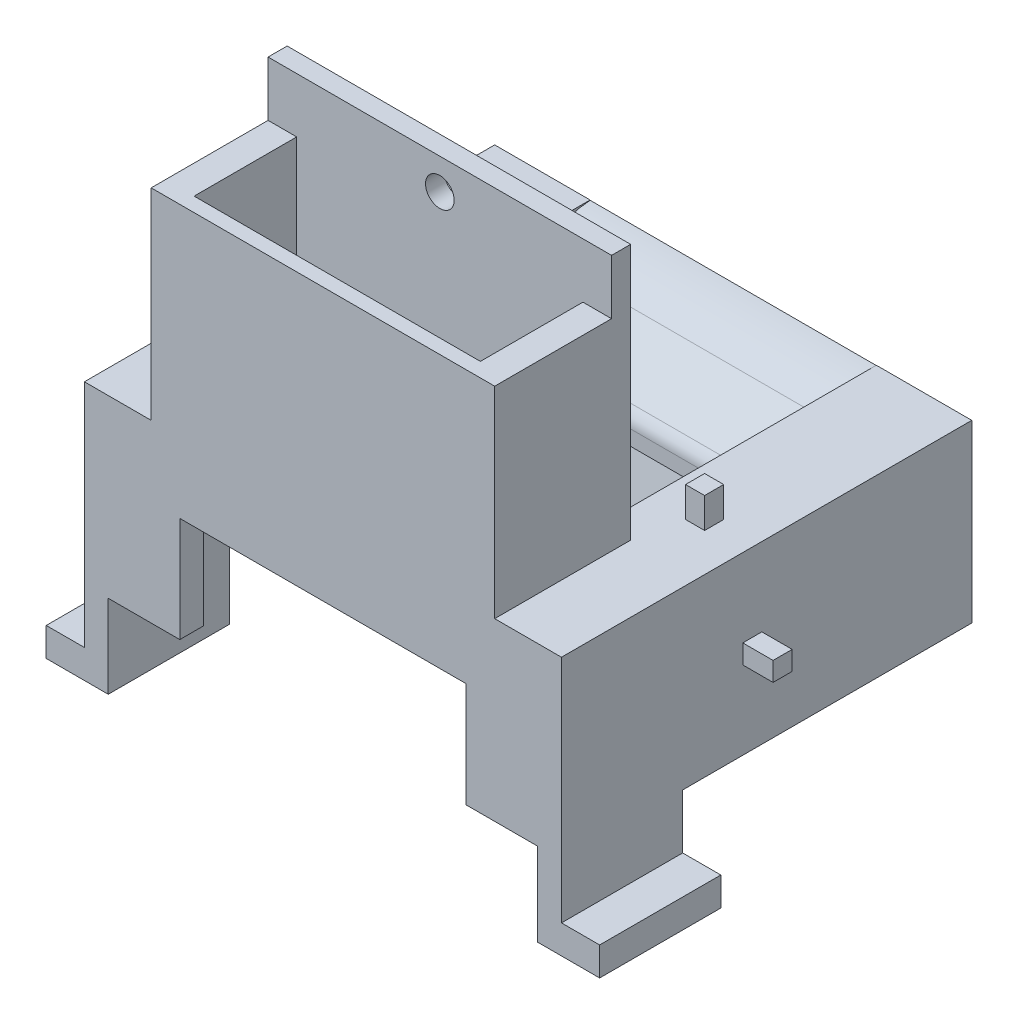
SolidWorks part; units mm, degrees
ref_plane "Front Plane" through (0, 0, 0) normal (0, 0, 1) x (1, 0, 0)
ref_plane "Top Plane" through (0, 0, 0) normal (0, 1, 0) x (1, 0, 0)
ref_plane "Right Plane" through (0, 0, 0) normal (1, 0, 0) x (0, 0, -1)
sketch "Sketch1" plane through (0, 0, 0) normal (0, 0, 1) x (1, 0, 0)
  line L1 (-25, 9.2) -> (25, 9.2)
  line L2 (-25, 9.2) -> (-25, -9.2)
  line L3 (-25, -9.2) -> (25, -9.2)
  line L4 (25, 9.2) -> (25, -9.2)
  line L5 (-25, 9.2) -> (25, -9.2) construction
  line L6 (-25, -9.2) -> (25, 9.2) construction
  point P0 (0, 0)
  dimension "D1" = 50
  dimension "D2" = 18.4
extrude "Boss-Extrude1" add sketch "Sketch1" along normal blind 43
sketch "Sketch2" plane through (0, -9.2, 0) normal (0, -1, 0) x (-1, 0, 0)
  line L0 (-25, -43) -> (-25, 0) construction
  line L1 (-22.5, -14.5) -> (-15, -14.5)
  line L2 (-22.5, -14.5) -> (-22.5, -9.5)
  line L3 (-22.5, -9.5) -> (-15, -9.5)
  line L4 (-15, -14.5) -> (-15, -9.5)
  line L5 (25, 0) -> (-25, 0) construction
  line L6 (22.5, -14.5) -> (15, -14.5)
  line L7 (22.5, -14.5) -> (22.5, -9.5)
  line L8 (22.5, -9.5) -> (15, -9.5)
  line L9 (15, -14.5) -> (15, -9.5)
  line L10 (-22.5, -12) -> (-25, -12) construction
  line L11 (15, -12.9) -> (-15, -12.9)
  line L12 (15, -12.9) -> (15, -11.1)
  line L13 (15, -11.1) -> (-15, -11.1)
  line L14 (-15, -12.9) -> (-15, -11.1)
  line L15 (22.5, -12) -> (25, -12) construction
  line L19 (25, -43) -> (25, 0) construction
  point P12 (15, -12)
  point P13 (-15, -12)
  point P15 (15, -12)
  line M14 (-25, 0) -> (-25, -43)
  line M16 (25, -43) -> (25, 0)
  dimension "D1" = 5
  dimension "D2" = 7.5
  dimension "D3" = 1.8
  dimension "D4" = 2.5
  dimension "IRdist" = 12
extrude "Cut-Extrude1" cut sketch "Sketch2" against normal blind 15.6 contours L9 L6 L8 M16 | L9 L13 L4 L11 | L1 L4 L3 M14 region at (18.75, -9.2, 12) region at (0, -9.2, 12) region at (-18.75, -9.2, 12)
sketch "Sketch3" plane through (0, 0, 0) normal (1, 0, 0) x (0, 0, -1)
  line L0 (-2.5, -9.2) -> (-2.5, 6.2)
  line L1 (-43, -9.2) -> (0, -9.2) construction
  line L2 (-2.5, 6.2) -> (-11.8253, -1.1447)
  line L3 (-11.8253, -1.1447) -> (-40.5, 6.2)
  line L4 (-40.5, 6.2) -> (-40.5, -9.2)
  line L5 (-40.5, -9.2) -> (-2.5, -9.2)
  line L6 (-43, 9.2) -> (0, 9.2) construction
  line L7 (-43, 9.2) -> (0, 9.2) construction
  line L8 (-43, 9.2) -> (-43, -9.2) construction
  line L9 (-2.7315, 9.2) -> (-12, 1.9)
  line L10 (-12, 1.9) -> (-40.5, 9.2)
  line L11 (-40.5, 9.2) -> (-2.7315, 9.2)
  line L12 (-14.5, 6.4) -> (-9.5, 6.4) construction
  line L13 (0, 9.2) -> (0, -9.2) construction
  line L14 (-21.6873, 4.3813) -> (-12, 1.6)
  line L15 (-12, 1.6) -> (-12, 1.9)
  dimension "D1" = 2.5
  dimension "D3" = 2.5
  dimension "D4" = 4.5
  dimension "D2" = 3
  dimension "D5" = 2.5
  dimension "D6" = 12
  dimension "D7" = 0.3
  dimension "D8" = 10
extrude "Cut-Extrude2" cut sketch "Sketch3" against normal up to vertex (22.5 mm away) contours L4 L5 L0 L2 L3 region at (0, -3.1445, 22.5098) up to point (-22.5, -9.2, 14.5)
mirror "Mirror3" about plane through (0, 0, 0) normal (1, 0, 0) of "Cut-Extrude2"
extrude "Cut-Extrude3" cut sketch "Sketch3<3>" against normal up to vertex (15 mm away) contours L11 L10 L9 | L14 L15 L10 region at (0, 6.7667, 18.4105) region at (0, 2.6271, 15.2291) up to point (-15, -0.8695, 12.9)
sketch "Sketch3<3>" plane through (0, 0, 0) normal (1, 0, 0) x (0, 0, -1) same geometry as "Sketch3"
mirror "Mirror4" about plane through (0, 0, 0) normal (1, 0, 0) of "Cut-Extrude3"
sketch "Sketch12" plane through (22.5, 0, 0) normal (-1, 0, 0) x (0, 0, 1)
  line L0 (9.5, 6.4) -> (9.5, 0.6867)
  line L1 (9.5, 0.6867) -> (9.625, 6.4)
  line L3 (9.625, 6.4) -> (9.5, 6.4)
  line L4 (14.5, 6.4) -> (14.5, 0.6867)
  line L5 (14.5, 0.6867) -> (14.375, 6.4)
  line L6 (14.375, 6.4) -> (14.5, 6.4)
  dimension "D1" = 4.75
extrude "Boss-Extrude3" add sketch "Sketch12" along normal up to surface (7.5 mm away) up to face at (15, 5.9669, 16.1312)
extrude "Boss-Extrude4" add sketch "Sketch12<2>" against normal up to surface (-37.5 mm away) from surface up to face at (-15, 1.6478, 10.3) starting at face at (-22.5, 0.8784, 16.75)
sketch "Sketch12<2>" plane through (22.5, 0, 0) normal (-1, 0, 0) x (0, 0, 1) same geometry as "Sketch12"
sketch "Sketch17" plane through (-15, 0, 0) normal (1, 0, 0) x (0, 0, -1)
  line L0 (-43, 9.2) -> (-43, 10.7)
  line L1 (-43, 10.7) -> (-21.6873, 4.3813)
  line L2 (-21.6873, 4.3813) -> (-40.5, 9.2)
  line L3 (-40.5, 9.2) -> (-43, 9.2)
  dimension "D1" = 1.5
extrude "Boss-Extrude7" add sketch "Sketch17" along normal up to surface (30 mm away) up to face at (15, 5.9577, 16.136)
sketch "Sketch18" plane through (15, 0, 0) normal (1, 0, 0) x (0, 0, -1)
  line L0 (-43, 10.7) -> (-43, 9.2)
  line L1 (-43, 9.2) -> (-37.9406, 9.2)
  line L2 (-43, 9.2) -> (-37.9406, 9.2) construction
  line L4 (-37.9406, 9.2) -> (-43, 10.7)
  line L5 (-43, 10.7) -> (-37.9406, 9.2) construction
extrude "Mtrl Rmv" cut sketch "Sketch18" against normal through all
ref_plane "Plane4" through (0, 0, 30.75) normal (0, 0, 1) x (1, 0, 0)
sketch "Sketch23" plane through (15, 0, 0) normal (-1, 0, 0) x (0, 0, 1)
  line L0 (21.6873, 4.3813) -> (14.4645, 2.3076) construction
  line L1 (30.75, -26.9374) -> (30.75, 26.9374) construction
  point P0 (30.75, 6.9833)
sketch "Sketch22" plane through (0, 0, 30.75) normal (0, 0, 1) x (1, 0, 0)
  line L0 (18, 36.05) -> (18, 11.9833)
  line L1 (18, 11.9833) -> (18, 9.2)
  line L2 (18, 36.05) -> (-18, 36.05)
  line L3 (18, 11.9833) -> (-18, 11.9833)
  line L4 (-18, 11.9833) -> (-18, 36.05)
  line L5 (15, 11.9833) -> (15, 6.9833) construction
  line L6 (15, 6.4) -> (15, 2.3076) construction
  line L7 (25, 9.2) -> (-25, 9.2) construction
  line L8 (15, 11.9833) -> (15, 9.2)
  line L9 (0, 11.9833) -> (0, 0) construction
  line L10 (18, 9.2) -> (15, 9.2)
  line L11 (-25, -9.2) -> (25, -9.2) construction
  line L12 (-18, 11.9833) -> (-18, 9.2)
  line L13 (-18, 9.2) -> (-15, 9.2)
  line L14 (-15, 9.2) -> (-15, 11.9833)
  dimension "D1" = 5
  dimension "D2" = 3
  dimension "D3" = 45.25
extrude "Boss-Extrude8" add sketch "Sketch22" against normal blind 2 contours L4 L3 L0 L2 | L10 L1 L3 L8 | L13 L14 L3 L12 region at (0, 24.0166, 30.75) region at (16.5, 10.5916, 30.75) region at (-16.5, 10.5916, 30.75)
sketch "Sketch25" plane through (18, 0, 0) normal (1, 0, 0) x (0, 0, -1)
  line L0 (-43, -9.2) -> (0, -9.2) construction
  line L1 (-43, 9.2) -> (-41.5, 9.2)
  line L2 (-43, 9.2) -> (-43, 30.3)
  line L3 (-43, 30.3) -> (-41.5, 30.3)
  line L4 (-41.5, 9.2) -> (-41.5, 30.3)
  line L5 (-35.7642, 18.6552) -> (-41.5, 23.3)
  line L6 (-35.7642, 18.6552) -> (-41.5, 18.6552)
  line L7 (-30.75, 18.6552) -> (-34.324, 11.9833)
  line L8 (-30.75, 36.05) -> (-30.75, 9.2) construction
  line L10 (-41.5, 10.2553) -> (-37.9406, 9.2)
  line L11 (-43, 9.2) -> (0, 9.2) construction
  line L12 (-21.6873, 4.3813) -> (-37.9406, 9.2) construction
  line L13 (-37.9406, 9.2) -> (-41.5, 9.2)
  line L14 (-34.324, 11.8778) -> (-37.9406, 9.2) construction
  line L15 (-35.7642, 18.6552) -> (-32.267, 15.8233) construction
  line L16 (-34.324, 11.8778) -> (-34.324, 8.1278) construction
  line L18 (-30.75, 11.9833) -> (-30.75, 6.9833) construction
  line L19 (-30.75, 36.05) -> (-30.75, 9.2) construction
  line L20 (-30.75, 11.9833) -> (-34.324, 11.9833)
  line L21 (-34.324, 11.8778) -> (-34.324, 11.9833) construction
  line L22 (-21.6873, 4.3813) -> (-14.4645, 2.3076) construction
  line M36 (-30.75, 36.05) -> (-30.75, 9.2)
  dimension "D1" = 1.5
  dimension "D2" = 39.5
  dimension "D3" = 3.75
  dimension "D4" = 51
  dimension "D5" = 7
  dimension "D6" = 4.5
  dimension "D7" = 4.5
  dimension "D8" = 5
extrude "Boss-Extrude9" add sketch "Sketch25" against normal up to surface (36 mm away) contours L1 L4 L3 L2 | L6 L5 L4 | L13 L10 L4 | M36 | L7 M36 region at (18, 19.75, 42.25) region at (18, 9.5518, 40.3135) region at (18, 20.2035, 39.5881) region at (18, 14.2073, 31.9413) up to face at (-18, 22.625, 29.75)
sketch "Sketch27" plane through (0, 0, 43) normal (0, 0, 1) x (1, 0, 0)
  line L0 (-18, 30.3) -> (18, 30.3) construction
  line L1 (-18, 9.2) -> (-15, 9.2)
  line L2 (-18, 9.2) -> (-18, 30.3)
  line L3 (-18, 30.3) -> (-15, 30.3)
  line L4 (-15, 9.2) -> (-15, 30.3)
  line L5 (25, 9.2) -> (18, 9.2) construction
  line L6 (18, 9.2) -> (15, 9.2)
  line L7 (18, 9.2) -> (18, 30.3)
  line L8 (18, 30.3) -> (15, 30.3)
  line L9 (15, 9.2) -> (15, 30.3)
extrude "Boss-Extrude10" add sketch "Sketch27" against normal up to surface (14.25 mm away) up to face at (0, 16.6083, 28.75)
sketch "Sketch28" plane through (0, 0, 28.75) normal (0, 0, -1) x (-1, 0, 0)
  line L0 (18, 30.3) -> (-18, 30.3) construction
  line L1 (-18, 36.05) -> (18, 36.05) construction
  circle A0 centre (0, 32.8) radius 1.5
  point P7 (0, 36.05)
  dimension "D1" = 3
  dimension "D2" = 2.5
extrude "Cut-Extrude4" cut sketch "Sketch28" against normal through all
sketch "Sketch4" plane through (0, 0, 43) normal (0, 0, 1) x (1, 0, 0)
  line L0 (-25, -9.2) -> (25, -9.2) construction
  line L1 (-15, -9.2) -> (15, -9.2)
  line L2 (-15, -9.2) -> (-15, 1.8)
  line L3 (-15, 1.8) -> (15, 1.8)
  line L4 (15, -9.2) -> (15, 1.8)
  point P6 (0, 1.8)
  dimension "D1" = 30
  dimension "D2" = 11
extrude "Wire Hole" cut sketch "Sketch4" against normal up to surface (2.5 mm away) up to face at (0, -1.5, 40.5)
sketch "Sketch13" plane through (0, 0, 0) normal (0, 0, -1) x (-1, 0, 0)
  line L0 (-13, 0) -> (13, 0) construction
  line L1 (-15, 1) -> (-13, 1)
  line L2 (-15, 1) -> (-15, -1)
  line L3 (-15, -1) -> (-13, -1)
  line L4 (-13, 1) -> (-13, -1)
  line L5 (13, 1) -> (15, 1)
  line L6 (13, 1) -> (13, -1)
  line L7 (13, -1) -> (15, -1)
  line L8 (15, 1) -> (15, -1)
  point P16 (0, 0)
  dimension "D1" = 2
  dimension "D2" = 7.5
extrude "Front Shield Pegs" add sketch "Sketch13" along normal blind 3.175
sketch "Sketch14" plane through (0, 9.2, 0) normal (0, 1, 0) x (1, 0, 0)
  line L0 (19, -23) -> (-19, -23) construction
  line L1 (21, -22) -> (19, -22)
  line L2 (21, -22) -> (21, -24)
  line L3 (21, -24) -> (19, -24)
  line L4 (19, -22) -> (19, -24)
  line L5 (-19, -22) -> (-21, -22)
  line L6 (-19, -22) -> (-19, -24)
  line L7 (-19, -24) -> (-21, -24)
  line L8 (-21, -22) -> (-21, -24)
  line L10 (25, -43) -> (18, -43) construction
  point P8 (0, -23)
  point P12 (21, -23)
  dimension "D1" = 2
  dimension "D2" = 20
  dimension "D3" = 4
extrude "Top Shield Pegs" add sketch "Sketch14" along normal blind 3.175
fillet "Fillet9" radius 10 1 edges at (0, 9.2, 2.7315)
fillet "Fillet10" radius 2 1 edges at (0, 2.6089, 11.1)
ref_plane "Plane3" through (0, 0, 19) normal (0, 0, 1) x (1, 0, 0)
sketch "Sketch19" plane through (0, 0, 19) normal (0, 0, 1) x (1, 0, 0)
  line L0 (22.5, -9.2) -> (22.5, -17.915)
  line L1 (22.5, -17.915) -> (29, -17.915)
  line L2 (29, -17.915) -> (29, -14.915)
  line L3 (29, -14.915) -> (25, -14.915)
  line L4 (25, -14.915) -> (25, -9.2)
  line L5 (25, -9.2) -> (22.5, -9.2)
  line L6 (-22.5, -9.2) -> (-22.5, -17.915)
  line L7 (-22.5, -17.915) -> (-29, -17.915)
  line L8 (-29, -17.915) -> (-29, -14.915)
  line L9 (-29, -14.915) -> (-25, -14.915)
  line L10 (-25, -14.915) -> (-25, -9.2)
  line L11 (-25, -9.2) -> (-22.5, -9.2)
  dimension "D1" = 4
  dimension "D2" = 5.715
  dimension "D3" = 3
extrude "Legs" add sketch "Sketch19" against normal blind 12.7 from surface starting at face at (0, 5.35, 43)
sketch "Sketch29" plane through (-25, 0, 0) normal (-1, 0, 0) x (0, 0, 1)
  line L0 (23, 1) -> (23, 12.375) construction
  line L1 (22, 1) -> (24, 1)
  line L2 (22, 1) -> (22, -1)
  line L3 (22, -1) -> (24, -1)
  line L4 (24, 1) -> (24, -1)
  line L5 (22, 12.375) -> (24, 12.375) construction
  line L7 (22, 12.375) -> (22, 9.2) construction
  line L8 (22, 0) -> (-3.175, 0) construction
  line L9 (-3.175, -1) -> (-3.175, 1) construction
extrude "Side Shield Pegs1" add sketch "Sketch29" along normal blind 3.175
extrude "Side Shield Pegs2" add sketch "Sketch29<2>" against normal blind 3.175 from surface starting at face at (25, -4.9717, 24.4333)
sketch "Sketch29<2>" plane through (-25, 0, 0) normal (-1, 0, 0) x (0, 0, 1) same geometry as "Sketch29"
fillet "Fillet3" [suppressed] radius 3
fillet "Fillet5" [suppressed] radius 3
fillet "Fillet6" [suppressed] radius 3 tangent propagation no
sketch "Sketch5" [suppressed] plane through (0, 0, 0) normal (1, 0, 0) x (0, 0, -1)
  line L0 (-40, 3.5229) -> (-61, 15.1419)
  line L1 (-45.2, 16.8) -> (-45.2, 18.347)
  line L2 (-61, 15.1419) -> (-61, 22.3)
  line L3 (-61, 22.3) -> (-45.2, 22.3)
  line L5 (-45.2, 16.8) -> (-40, 13.9229)
  line L6 (-40, 13.9229) -> (-40, 3.5229)
  line L7 (-40, 6.2) -> (-40, -9.2) construction
  line L8 (-45.2, 18.347) -> (-45.2, 22.3)
  line L10 (0, 9.2) -> (-40, 9.2) construction
  line L11 (-45.2, 22.3) -> (-61, 22.3)
  line L12 (-45.2, 22.3) -> (-45.2, 30.675)
  line L13 (-45.2, 30.675) -> (-61, 30.675)
  line L14 (-61, 22.3) -> (-61, 30.675)
  line L19 (-40, 13.9229) -> (-35.4398, 11.3998)
  line L20 (-35.4398, 11.3998) -> (-35.4398, 9.2)
  line L22 (-35.4398, 9.2) -> (-40, 9.2)
  dimension "D1" = 24
  dimension "D2" = 21
  dimension "D3" = 13.1
  dimension "D4" = 5.2
  dimension "D5" = 5.5
  dimension "D6" = 10.4
  dimension "D7" = 8.375
extrude "Ramp Extrude" [suppressed] add sketch "Sketch5" along normal mid plane 15
ref_plane "Plane2" [suppressed] through (0, 7.2819, -2.3953) normal (0, 0.9499, -0.3125) x (1, 0, 0)
sketch "Sketch7" [suppressed] plane through (0, 0, 0) normal (1, 0, 0) x (0, 0, -1)
  line L1 (-61, 15.1419) -> (-61, 30.675) construction
  line L2 (-60, 19.3) -> (-60, 22.3)
  line L3 (-60, 22.3) -> (-45.2, 22.3)
  line L4 (-60, 22.3) -> (-45.2, 22.3)
  line L5 (-45.2, 22.3) -> (-45.2, 16.8)
  line L8 (-60, 22.3) -> (-60, 30.675)
  line L9 (-35.4398, 11.3998) -> (-35.4398, 9.2)
  line L10 (-45.2, 27.675) -> (-60, 27.675) construction
  line L11 (-60, 30.675) -> (-45.2, 30.675)
  line L12 (-45.2, 22.3) -> (-45.2, 30.675)
  line L13 (-45.2, 30.675) -> (-61, 30.675) construction
  line L14 (-45.2, 16.8) -> (-45.2, 30.675) construction
  line L17 (-45.2, 16.8) -> (-35.4398, 11.3998)
  line L21 (-35.4398, 9.2) -> (-54.0763, 18.2247)
  arc A0 (-60, 27.675) -> (-54.0763, 18.2247) centre (-49.5, 27.675) ccw
  dimension "D5" = 10.5
  dimension "D1" = 1
  dimension "D2" = 3
  dimension "D3" = 5.5
  dimension "D4" = 3
extrude "Ramp Shell Cut" [suppressed] cut sketch "Sketch7" against normal mid plane 13
sketch "Sketch8" [suppressed] plane through (-7.5, 0, 0) normal (-1, 0, 0) x (0, 0, 1)
  line L0 (45.2, 23.7375) -> (49.15, 30.675)
  line L1 (45.2, 16.8) -> (45.2, 30.675) construction
  line L2 (45.2, 30.675) -> (61, 30.675) construction
  line L3 (49.15, 30.675) -> (45.2, 30.675)
  line L4 (45.2, 30.675) -> (45.2, 23.7375)
  line L5 (45.2, 23.7375) -> (53.1, 23.7375) construction
  point P9 (53.1, 30.675)
  point P12 (49.15, 23.7375)
extrude "Ramp Corner Cuts" [suppressed] cut sketch "Sketch8" against normal through all
equation "\"bottomThickness\"= .220in"
equation "\"wallThickness\"= .125in"
equation "\"D1@Front Shield Pegs\" = \"wallThickness\""
equation "\"D1@Top Shield Pegs\" = \"wallThickness\""
equation "\"IRdist\"=12"
equation "\"IRdist@Sketch2\"=\"IRdist\""
equation "\"D6@Sketch3\"=\"IRdist\""
equation "\"D1@Side Shield Pegs1\" = \"wallThickness\""
equation "\"D1@Side Shield Pegs2\" = \"wallThickness\""
equation "\"D2@Sketch19\"=\"bottomThickness\"+.005in"
